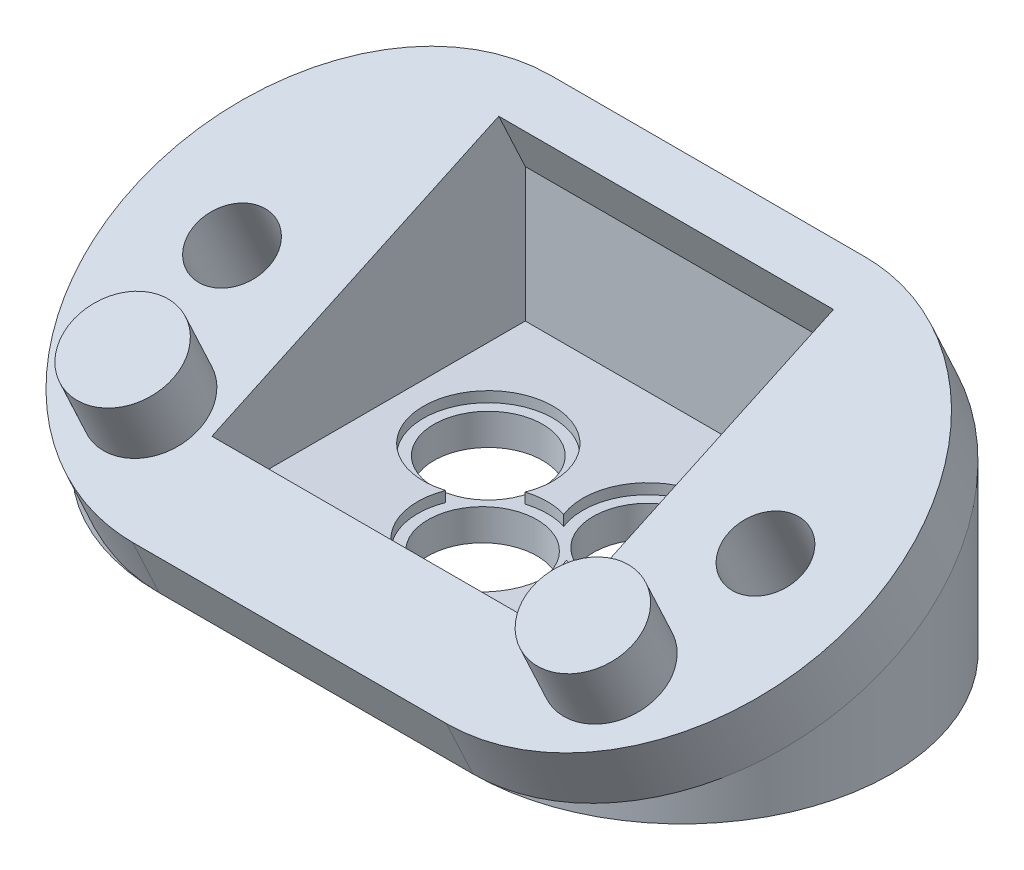
SolidWorks part; units mm, degrees
ref_plane "Front Plane" through (0, 0, 0) normal (0, 0, 1) x (1, 0, 0)
ref_plane "Top Plane" through (0, 0, 0) normal (0, 1, 0) x (1, 0, 0)
ref_plane "Right Plane" through (0, 0, 0) normal (1, 0, 0) x (0, 0, -1)
sketch "Sketch1" plane through (0, 0, 0) normal (0, 1, 0) x (1, 0, 0)
  line L0 (-7.5, 0) -> (7.5, 0) construction
  line L1 (-7.5, 10) -> (7.5, 10)
  line L2 (-7.5, -10) -> (7.5, -10)
  line L3 (-3.81, 2.0429) -> (3.81, 2.0429) construction
  line L4 (0, -2.0429) -> (-3.81, 2.0429) construction
  line L5 (0, -2.0429) -> (3.81, 2.0429) construction
  line L6 (0, -2.0429) -> (0, 2.0429) construction
  arc A0 (-7.5, 10) -> (-7.5, -10) centre (-7.5, 0) ccw
  arc A1 (7.5, -10) -> (7.5, 10) centre (7.5, 0) ccw
  circle A2 centre (-3.81, 2.0429) radius 2.6
  circle A3 centre (3.81, 2.0429) radius 2.6
  circle A4 centre (0, -2.0429) radius 2.6
  point P2 (0, 0)
  point P13 (0, 0)
  point P15 (0, 2.0429)
  dimension "D2" = 10
  dimension "D3" = 5.2
  dimension "D4" = 5.2
  dimension "D5" = 5.2
  dimension "D1" = 15
  dimension "D6" = 7.62
  dimension "D7" = 47
  dimension "D8" = 47
extrude "Boss-Extrude3" add sketch "Sketch1" along normal blind 20
sketch "Sketch2" plane through (0, 20, 0) normal (0, 1, 0) x (1, 0, 0)
  line L1 (-8, 8) -> (8, 8)
  line L2 (-8, 8) -> (-8, -8)
  line L3 (-8, -8) -> (8, -8)
  line L4 (8, 8) -> (8, -8)
  line L5 (-8, 8) -> (8, -8) construction
  line L6 (-8, -8) -> (8, 8) construction
  point P0 (0, 0)
  dimension "D1" = 16
  dimension "D2" = 16
extrude "Cut-Extrude1" cut sketch "Sketch2" against normal offset from surface (18 mm away) 2 up to face at (0, 0, 0)
sketch "Sketch4" plane through (-8, 0, 0) normal (1, 0, 0) x (0, 0, -1)
  line L0 (-10, 0) -> (10, 9.3262)
  line L1 (10, 20) -> (10, 0) construction
  line L6 (-10, 0) -> (10, 0)
  line L7 (-10, 20) -> (-10, 0)
  line L8 (10, 20) -> (-10, 20)
  line L9 (10, 0) -> (10, 20)
  line L10 (-10, 0) -> (10, 0)
  line L11 (-10, 20) -> (-10, 0)
  line L12 (10, 20) -> (-10, 20)
  line L13 (10, 0) -> (10, 20)
  line M6 (-8, 2) -> (8, 2)
  line M7 (8, 2) -> (8, 20)
  line M8 (8, 20) -> (-8, 20)
  line M9 (-8, 20) -> (-8, 2)
  dimension "D2" = 65
  dimension "D1" = 0
extrude "Cut-Extrude2" cut sketch "Sketch4" against normal through all both and the other way through all contours L0 M6 M7 M8 M9 | L0 L13 L12 M7 | L12 L11 L0 M9 M6 region at (-8, 9.9709, 8.9543) region at (-8, 12.233, 0.6157) region at (-8, 14.4267, -8.986)
sketch "Sketch5" plane through (0, 3.8302, 1.7861) normal (0, 0.9063, 0.4226) x (1, 0, 0)
  line L0 (-12.75, 1.9707) -> (-17.5, 1.9707) construction
  line L1 (-12.75, 1.9707) -> (-8, 1.9707) construction
  line L2 (-8, 10.7977) -> (-8, -4.3307) construction
  line L3 (0, -9.0631) -> (0, 13.0045) construction
  line L4 (-7.5, -9.0631) -> (7.5, -9.0631) construction
  line L5 (-7.5, 13.0045) -> (7.5, 13.0045) construction
  circle A0 centre (-12.75, 1.9707) radius 1.75
  circle A2 centre (12.75, 1.9707) radius 1.75
  dimension "D1" = 3.5
extrude "Cut-Extrude3" cut sketch "Sketch5" against normal through all and the other way through all
sketch "Sketch7" plane through (0, 3.8302, 1.7861) normal (0, 0.9063, 0.4226) x (1, 0, 0)
  line L0 (0, 13.0045) -> (0, -9.0631) construction
  line L1 (-7.5, 13.0045) -> (7.5, 13.0045) construction
  line L2 (-7.5, -9.0631) -> (7.5, -9.0631) construction
  circle A0 centre (-12.75, 1.9707) radius 2.5
  circle A1 centre (12.75, 1.9707) radius 2.5
  circle A2 centre (12.75, 1.9707) radius 1.75 construction
  circle A3 centre (-12.75, 1.9707) radius 1.75 construction
  circle A4 centre (12.75, 1.9707) radius 1.75
  circle A5 centre (-12.75, 1.9707) radius 1.75
  dimension "D1" = 5
extrude "Boss-Extrude4" add sketch "Sketch7" against normal blind 4
extrude "Cut-Extrude6" cut sketch "Sketch7<5>" against normal up to surface (0.3291 mm away) from offset 4 contours A4 | A1 | A5 | A0 up to face at (12.75, 0, 0.5596) offset against normal yes
sketch "Sketch7<5>" plane through (0, 3.8302, 1.7861) normal (0, 0.9063, 0.4226) x (1, 0, 0) same geometry as "Sketch7"
sketch "Sketch9" plane through (0, 3.8302, 1.7861) normal (0, 0.9063, 0.4226) x (1, 0, 0)
  line L0 (8, -4.3307) -> (-8, -4.3307) construction
  line L1 (-11, -4.3307) -> (-8, -4.3307) construction
  line L2 (0, -9.0631) -> (0, 13.0045) construction
  line L3 (-7.5, -9.0631) -> (7.5, -9.0631) construction
  line L4 (-7.5, 13.0045) -> (7.5, 13.0045) construction
  circle A0 centre (-11, -4.3307) radius 2.4
  circle A1 centre (11, -4.3307) radius 2.4
  dimension "D1" = 4.8
  dimension "D2" = 3
extrude "Boss-Extrude5" add sketch "Sketch9" along normal blind 3
sketch "Sketch11" plane through (0, 2, 0) normal (0, 1, 0) x (1, 0, 0)
  arc A0 (-0.9217, 0.9169) -> (-2.8883, -0.9169) centre (-3.81, 2.0429) ccw
  arc A1 (2.8883, -0.9169) -> (0.9217, 0.9169) centre (3.81, 2.0429) ccw
  arc A2 (-2.8883, -0.9169) -> (2.8883, -0.9169) centre (0, -2.0429) ccw
  circle A3 centre (-3.81, 2.0429) radius 2.6 construction
  circle A4 centre (3.81, 2.0429) radius 2.6 construction
  circle A5 centre (0, -2.0429) radius 2.6 construction
  arc A6 (0.9217, 0.9169) -> (-0.9217, 0.9169) centre (0, -2.0429) ccw
  circle M9 centre (-3.81, 2.0429) radius 2.6
  circle M10 centre (3.81, 2.0429) radius 2.6
  circle M11 centre (0, -2.0429) radius 2.6
  dimension "D1" = 6.2
  dimension "D2" = 6.2
  dimension "D3" = 6.2
extrude "Cut-Extrude10" cut sketch "Sketch11" against normal blind 0.5 contours A1 A6 A0 A2 M10 M11 M9 region at (0, 2, -0.7424)
sketch "Sketch14" plane through (0, 3.8302, 1.7861) normal (0, 0.9063, 0.4226) x (1, 0, 0)
  circle A0 centre (11, -4.3307) radius 2.4 construction
  circle A1 centre (-11, -4.3307) radius 2.4 construction
  circle A2 centre (-12.75, 1.9707) radius 1.75 construction
  circle A3 centre (12.75, 1.9707) radius 1.75 construction
  circle A4 centre (11, -4.3307) radius 2.4
  circle A5 centre (-11, -4.3307) radius 2.4
  circle A6 centre (-12.75, 1.9707) radius 1.75
  circle A7 centre (12.75, 1.9707) radius 1.75
sketch "Sketch18" plane through (0, 3.8302, 1.7861) normal (0, 0.9063, 0.4226) x (1, 0, 0)
  line L0 (-7.5, -9.0631) -> (7.5, -9.0631) construction
  line L1 (7.5, 13.0045) -> (-7.5, 13.0045) construction
  line L2 (8, 10.7977) -> (-8, 10.7977) construction
  line L3 (-8, 10.7977) -> (-8, -4.3307) construction
  line L4 (8, -4.3307) -> (-8, -4.3307) construction
  line L5 (8, -4.3307) -> (8, 10.7977) construction
  line L6 (-7.5, -9.0631) -> (7.5, -9.0631)
  line L7 (7.5, 13.0045) -> (-7.5, 13.0045)
  line L8 (8, 10.7977) -> (-8, 10.7977)
  line L9 (-8, 10.7977) -> (-8, -4.3307)
  line L10 (8, -4.3307) -> (-8, -4.3307)
  line L11 (8, -4.3307) -> (8, 10.7977)
  circle A0 centre (11, -4.3307) radius 2.4 construction
  circle A1 centre (-11, -4.3307) radius 2.4 construction
  circle A2 centre (-12.75, 1.9707) radius 1.75 construction
  circle A3 centre (11, -4.3307) radius 2.4
  circle A4 centre (-11, -4.3307) radius 2.4
  circle A5 centre (-12.75, 1.9707) radius 1.75
  circle A6 centre (12.75, 1.9707) radius 1.75 construction
  circle A7 centre (12.75, 1.9707) radius 1.75
  ellipse E0 centre (7.5, 1.9707) end of major axis (7.5, 13.0045) minor radius 10 (7.5, -9.0631) -> (7.5, 13.0045) ccw construction
  ellipse E1 centre (-7.5, 1.9707) end of major axis (-7.5, -9.0631) minor radius 10 (-7.5, 13.0045) -> (-7.5, -9.0631) ccw construction
  ellipse E2 centre (7.5, 1.9707) end of major axis (7.5, -9.0631) minor radius 10 (7.5, -9.0631) -> (7.5, 13.0045) ccw
  ellipse E3 centre (-7.5, 1.9707) end of major axis (-7.5, -9.0631) minor radius 10 (-7.5, 13.0045) -> (-7.5, -9.0631) ccw
extrude "Boss-Extrude9" add sketch "Sketch18" along normal blind 3
extrude "Boss-Extrude10" add sketch "Sketch9<2>" along normal blind 6
sketch "Sketch9<2>" plane through (0, 3.8302, 1.7861) normal (0, 0.9063, 0.4226) x (1, 0, 0) same geometry as "Sketch9"
equation "\"D4@Sketch1\"=\"D3@Sketch1\""
equation "\"D5@Sketch1\"=\"D3@Sketch1\""
